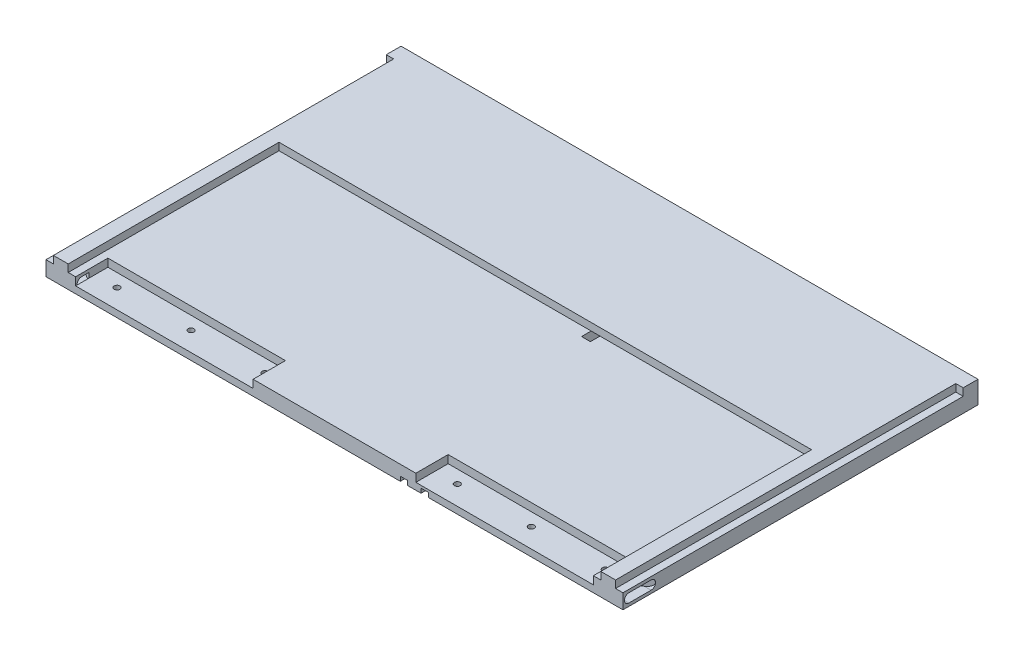
SolidWorks part; units mm, degrees
other "Markup1"
sketch "Sketch12" plane through (250.825, 22.225, 158.75) normal (0.1153, 0.0728, 0.9907) x (0.9687, -0.2289, -0.0959)
material "6061 Alloy"
ref_plane "Front Plane" through (0, 0, 0) normal (0, 0, 1) x (1, 0, 0)
ref_plane "Top Plane" through (0, 0, 0) normal (0, 1, 0) x (1, 0, 0)
ref_plane "Right Plane" through (0, 0, 0) normal (1, 0, 0) x (0, 0, -1)
sketch "Sketch1" plane through (0, 0, 0) normal (0, 1, 0) x (1, 0, 0)
  line L1 (-241.3, 152.4) -> (241.3, 152.4)
  line L2 (-241.3, 152.4) -> (-241.3, -152.4)
  line L3 (-241.3, -152.4) -> (241.3, -152.4)
  line L4 (241.3, 152.4) -> (241.3, -152.4)
  line L5 (-241.3, 152.4) -> (241.3, -152.4) construction
  line L6 (-241.3, -152.4) -> (241.3, 152.4) construction
  circle A0 centre (-203.2, -135.8392) radius 2.5019 construction
  circle A1 centre (-139.7, -135.8392) radius 2.5019 construction
  circle A2 centre (-76.2, -135.8392) radius 2.5019 construction
  circle A3 centre (88.9, -135.8392) radius 2.5019 construction
  circle A4 centre (152.4, -135.8392) radius 2.5019 construction
  circle A5 centre (215.9, -135.8392) radius 2.5019 construction
  circle A6 centre (-203.2, -135.8392) radius 2.5019
  circle A7 centre (-139.7, -135.8392) radius 2.5019
  circle A8 centre (-76.2, -135.8392) radius 2.5019
  circle A9 centre (88.9, -135.8392) radius 2.5019
  circle A10 centre (152.4, -135.8392) radius 2.5019
  circle A11 centre (215.9, -135.8392) radius 2.5019
  point P0 (0, 0)
  dimension "D1" = 482.6
  dimension "D2" = 304.8
extrude "Boss-Extrude1" add sketch "Sketch1" along normal blind 12.7
sketch "Sketch2" plane through (0, 12.7, 0) normal (0, 1, 0) x (1, 0, 0)
  line L0 (-241.3, -152.4) -> (241.3, -152.4) construction
  line L1 (-241.3, 152.4) -> (-228.6, 152.4)
  line L2 (-241.3, 152.4) -> (-241.3, -152.4)
  line L3 (-241.3, -152.4) -> (-228.6, -152.4)
  line L4 (-228.6, 28.575) -> (-228.6, -152.4)
  line L5 (241.3, 152.4) -> (-241.3, 152.4) construction
  line L6 (241.3, 152.4) -> (228.6, 152.4)
  line L7 (241.3, 152.4) -> (241.3, -152.4)
  line L8 (241.3, -152.4) -> (228.6, -152.4)
  line L9 (228.6, 28.575) -> (228.6, -152.4)
  line L10 (-228.6, 152.4) -> (228.6, 152.4)
  line L12 (-228.6, 28.575) -> (228.6, 28.575)
  point P14 (-234.95, -152.4)
  dimension "D1" = 12.7
  dimension "D2" = 180.975
extrude "Boss-Extrude2" add sketch "Sketch2" along normal blind 6.35
sketch "Sketch3" plane through (-241.3, 0, 0) normal (-1, 0, 0) x (0, 0, 1)
  line L0 (152.4, 19.05) -> (152.4, 0) construction
  line L1 (-152.4, 19.05) -> (152.4, 19.05) construction
  circle A0 centre (149.225, 15.875) radius 1.5875
  dimension "D3" = 3.175
  dimension "D1" = 3.175
  dimension "D2" = 3.175
sketch "Sketch4" plane through (0, 0, 152.4) normal (0, 0, 1) x (1, 0, 0)
  line L0 (-241.3, 19.05) -> (-241.3, 0) construction
  line L1 (-241.3, 12.7) -> (-247.65, 12.7)
  line L2 (-241.3, 12.7) -> (-241.3, 0)
  line L3 (-241.3, 0) -> (-247.65, 0)
  line L4 (-247.65, 12.7) -> (-247.65, 0)
  line L5 (-241.3, 0) -> (241.3, 0) construction
  dimension "D1" = 12.7
  dimension "D2" = 6.35
extrude "Boss-Extrude3" add sketch "Sketch4" against normal blind 292.1
sketch "Sketch5" plane through (-241.3, 0, 0) normal (-1, 0, 0) x (0, 0, 1)
  line L0 (-152.4, 0) -> (-139.7, 0) construction
  line L1 (-152.4, 19.05) -> (-139.7, 19.05)
  line L2 (-152.4, 19.05) -> (-152.4, 0)
  line L3 (-152.4, 0) -> (-139.7, 0)
  line L4 (-139.7, 19.05) -> (-139.7, 0)
  line L5 (-139.7, 0) -> (-139.7, 12.7) construction
extrude "Boss-Extrude4" add sketch "Sketch5" along normal up to surface (6.35 mm away) up to face at (-247.65, 6.35, 6.35)
mirror "Mirror1" about plane through (0, 0, 0) normal (1, 0, 0) of "Boss-Extrude4", "Boss-Extrude3"
sketch "Sketch6" plane through (-241.3, 0, 0) normal (-1, 0, 0) x (0, 0, 1)
  line L0 (147.32, 6.35) -> (128.27, 6.35) construction
  line L1 (147.32, 2.54) -> (128.27, 2.54)
  line L2 (147.32, 10.16) -> (128.27, 10.16)
  line L3 (152.4, 19.05) -> (152.4, 12.7) construction
  line L5 (152.4, 12.7) -> (152.4, 0) construction
  arc A0 (147.32, 2.54) -> (147.32, 10.16) centre (147.32, 6.35) ccw
  arc A1 (128.27, 10.16) -> (128.27, 2.54) centre (128.27, 6.35) ccw
  point P2 (137.795, 6.35)
  point P11 (152.4, 6.35)
  dimension "D1" = 19.05
  dimension "D2" = 5.08
  dimension "D3" = 7.62
extrude "Cut-Extrude2" cut sketch "Sketch6" against normal blind 25.4 from surface starting at face at (-247.65, 10.5833, -46.5667)
extrude "Cut-Extrude3" cut sketch "Sketch6<2>" along normal blind 25.4 from surface starting at face at (247.65, 10.5833, -46.5667)
sketch "Sketch6<2>" plane through (-241.3, 0, 0) normal (-1, 0, 0) x (0, 0, 1) same geometry as "Sketch6"
sketch "Sketch11" plane through (0, 0, 0) normal (0, -1, 0) x (1, 0, 0)
  line L0 (-247.65, 124.46) -> (-222.25, 124.46)
  line L1 (-222.25, 124.46) -> (-222.25, 140.97)
  line L2 (-222.25, 140.97) -> (-247.65, 124.46)
  line L3 (-222.25, 128.27) -> (-222.25, 147.32) construction
  dimension "D1" = 10.16
extrude "Boss-Extrude5" add sketch "Sketch11" against normal up to surface (10.16 mm away) from surface up to face at (-234.95, 10.16, 137.795) starting at face at (-234.95, 2.54, 137.795)
mirror "Mirror2" about plane through (0, 0, 0) normal (1, 0, 0) of "Boss-Extrude5"
sketch "Sketch13" plane through (0, 12.7, 0) normal (0, 1, 0) x (1, 0, 0)
  line L0 (228.6, 28.575) -> (228.6, -152.4) construction
  line L1 (222.25, -152.4) -> (69.85, -152.4)
  line L2 (222.25, -152.4) -> (222.25, -124.6632)
  line L3 (222.25, -124.6632) -> (69.85, -124.6632)
  line L4 (69.85, -152.4) -> (69.85, -124.6632)
  line L5 (-228.6, -152.4) -> (228.6, -152.4) construction
  line L6 (0, 0) -> (0, -222.4022) construction
  line L7 (-222.25, -152.4) -> (-222.25, -124.6632)
  line L8 (-222.25, -152.4) -> (-69.85, -152.4)
  line L9 (-69.85, -152.4) -> (-69.85, -124.6632)
  line L10 (-222.25, -124.6632) -> (-69.85, -124.6632)
  dimension "D1" = 27.7368
  dimension "D2" = 6.35
  dimension "D3" = 152.4
extrude "Cut-Extrude4" cut sketch "Sketch13" against normal blind 6.8072
sketch "Sketch14" plane through (0, 0, 0) normal (0, -1, 0) x (1, 0, 0)
  line L1 (39.37, -20.32) -> (46.99, -20.32)
  line L2 (39.37, -20.32) -> (39.37, -39.37)
  line L3 (39.37, -39.37) -> (46.99, -39.37)
  line L4 (46.99, -20.32) -> (46.99, -39.37)
  line L7 (247.65, -152.4) -> (-247.65, -152.4) construction
  line L10 (247.65, -152.4) -> (247.65, 152.4) construction
  dimension "D1" = 200.66
  dimension "D2" = 7.62
  dimension "D3" = 19.05
  dimension "D4" = 113.03
extrude "Cut-Extrude5" cut sketch "Sketch14" against normal blind 12.7
sketch "Sketch15" plane through (0, 0, 0) normal (0, -1, 0) x (1, 0, 0)
  line L0 (247.65, -152.4) -> (-247.65, -152.4) construction
  line L1 (80.6637, -152.4) -> (74.3137, -152.4)
  line L2 (80.6637, -152.4) -> (80.6637, 152.4)
  line L3 (80.6637, 152.4) -> (74.3137, 152.4)
  line L4 (74.3137, -152.4) -> (74.3137, 152.4)
  line L5 (-247.65, 152.4) -> (247.65, 152.4) construction
  line L6 (46.99, -39.37) -> (46.99, -20.32) construction
  line L7 (62.8837, -152.4) -> (56.5337, -152.4)
  line L8 (62.8837, -152.4) -> (62.8837, 152.4)
  line L9 (62.8837, 152.4) -> (56.5337, 152.4)
  line L10 (56.5337, -152.4) -> (56.5337, 152.4)
  point P12 (77.4887, -152.4)
  point P13 (59.7087, -152.4)
  dimension "D1" = 6.35
  dimension "D2" = 6.35
  dimension "D3" = 17.78
  dimension "D4" = 12.7187
extrude "Cut-Extrude6" cut sketch "Sketch15" against normal blind 3.81
